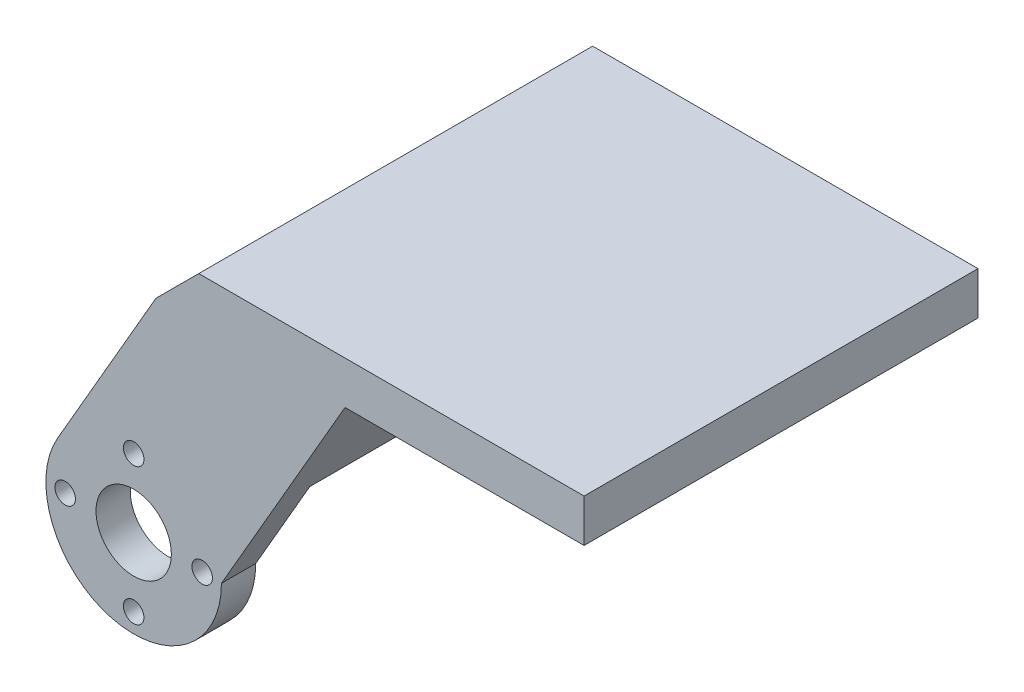
SolidWorks part; units mm, degrees
ref_plane "Front Plane" through (0, 0, 0) normal (0, 0, 1) x (1, 0, 0)
ref_plane "Top Plane" through (0, 0, 0) normal (0, 1, 0) x (1, 0, 0)
ref_plane "Right Plane" through (0, 0, 0) normal (1, 0, 0) x (0, 0, -1)
sketch "Sketch1" plane through (0, 0, 0) normal (0, 0, 1) x (1, 0, 0)
  line L0 (0, 0) -> (14.4338, 25) construction
  line L2 (10.25, 0) -> (-10.25, 0)
  line L3 (10.25, 0) -> (10.25, 25)
  line L6 (10.25, 25) -> (-10.25, 25)
  line L9 (-10.25, 0) -> (-10.25, 25)
  line L10 (-10.25, 25) -> (10.25, 25)
  line L15 (-8.8768, 5.125) -> (2.5981, 25)
  line L17 (5.4848, 30) -> (5.557, 30.125)
  line L18 (2.5981, 25) -> (52.5981, 25)
  line L19 (2.5981, 25) -> (2.5981, 30)
  line L20 (2.5981, 30) -> (52.5981, 30)
  line L21 (52.5981, 25) -> (52.5981, 30)
  line L22 (10.25, 0) -> (24.6838, 25)
  circle A0 centre (0, 0) radius 10.25
  circle A5 centre (0, 0) radius 4.4
  circle A6 centre (0, 0) radius 8
  circle A7 centre (0, 8) radius 1.2
  circle A8 centre (8, 0) radius 1.2
  circle A9 centre (0, -8) radius 1.2
  circle A10 centre (-8, 0) radius 1.2
  arc A13 (-8.8768, 5.125) -> (8.8768, -5.125) centre (0, 0) ccw
  point P4 (7.2169, 12.5)
  point P36 (0, 0)
  dimension "D1" = 25
  dimension "D4" = 0
  dimension "D5" = 5
  dimension "D7" = 8.8
  dimension "D8" = 2.4
  dimension "D2" = 10.25
  dimension "D3" = 60
  dimension "D6" = 50
  dimension "D10" = 60
  dimension "D9" = 4
extrude "Boss-Extrude1" add sketch "Sketch1" against normal blind 46 contours A0 L3 L6 L9 | A10 A6 A7 A8 L2 A0 | A10 L2 A5 A8 A6 A7 | A10 L2 A0 A8 A6 A9 | A10 A6 A9 A8 L2 A5 | L18 L21 L20 L19 L6 | L0 L3 L22 L18 | L3 L0 L18 | L0 A0 L3 | L0 A6 A8 L2 A0 | L0 A5 L2 A8 A6
sketch "Sketch3" plane through (-8.8768, 5.125, 0) normal (-0.866, 0.5, 0) x (0, 0, 1)
  line L0 (-46, -10.25) -> (0, -10.25) construction
  line L1 (-4, -10.25) -> (-42, -10.25)
  line L2 (-4, -10.25) -> (-4, 17.75)
  line L3 (-4, 17.75) -> (-42, 17.75)
  line L4 (-42, -10.25) -> (-42, 17.75)
  line L5 (-46, 0) -> (-46, 22.9497) construction
  dimension "D1" = 28
  dimension "D2" = 4
  dimension "D3" = 4
extrude "Cut-Extrude2" cut sketch "Sketch3" against normal through all
chamfer "Chamfer1" distance 5 angle 45 1 edges at (2.5981, 30, -23)
